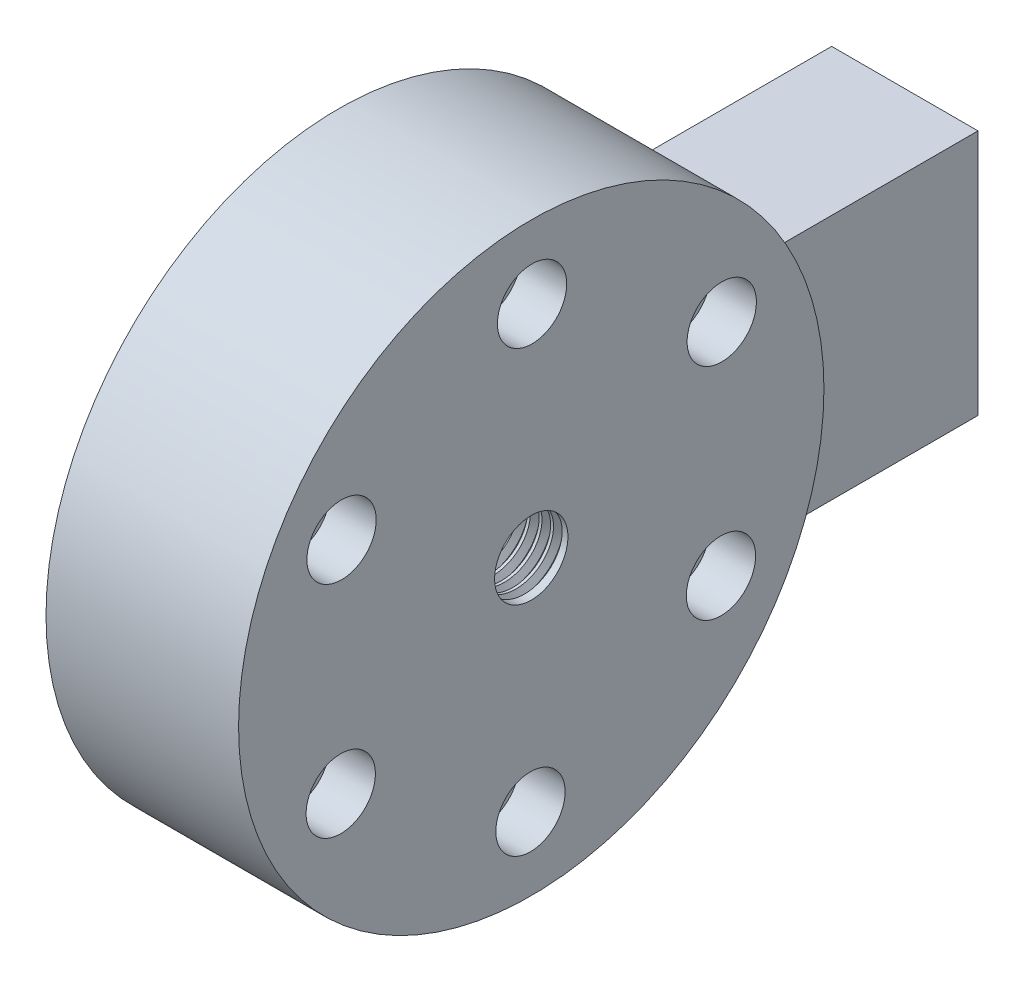
SolidWorks part; units mm, degrees
ref_plane "Front Plane" through (0, 0, 0) normal (0, 0, 1) x (1, 0, 0)
ref_plane "Top Plane" through (0, 0, 0) normal (0, 1, 0) x (1, 0, 0)
ref_plane "Right Plane" through (0, 0, 0) normal (1, 0, 0) x (0, 0, -1)
sketch "Sketch1" plane through (0, 0, 0) normal (1, 0, 0) x (0, 0, -1)
  circle A0 centre (0, 0) radius 38
  dimension "D1" = 76
extrude "Boss-Extrude1" add sketch "Sketch1" along normal blind 25
sketch "Sketch2" plane through (25, 0, 0) normal (1, 0, 0) x (0, 0, -1)
  circle A0 centre (0.1038, 28.4998) radius 3.5
  circle A2 centre (24.7335, 14.16) radius 3.5
  circle A3 centre (24.6297, -14.3398) radius 3.5
  circle A4 centre (-0.1038, -28.4998) radius 3.5
  circle A5 centre (-24.7335, -14.16) radius 3.5
  circle A6 centre (-24.6297, 14.3398) radius 3.5
  circle A9 centre (0, 0) radius 28.5 construction
  dimension "D1" = 7
  dimension "D2" = 57
  dimension "D3" = 6
extrude "Cut-Extrude1" cut sketch "Sketch2" against normal blind 25 contours A0 | A2 | A3 | A4 | A5 | A6
sketch "Sketch3" plane through (25, 0, 0) normal (1, 0, 0) x (0, 0, -1)
  circle A0 centre (0.1038, 28.4998) radius 4.5
  circle A1 centre (0, 0) radius 28.5 construction
  circle A2 centre (0, 0) radius 28.5 construction
  circle A3 centre (24.7335, 14.16) radius 4.5
  circle A4 centre (0, 0) radius 28.5 construction
  circle A5 centre (24.6297, -14.3398) radius 4.5
  circle A6 centre (0, 0) radius 28.5 construction
  circle A7 centre (-0.1038, -28.4998) radius 4.5
  circle A8 centre (0, 0) radius 28.5 construction
  circle A9 centre (-24.7335, -14.16) radius 4.5
  circle A10 centre (0, 0) radius 28.5 construction
  circle A11 centre (-24.6297, 14.3398) radius 4.5
  dimension "D1" = 9
  dimension "D2" = 6
extrude "Cut-Extrude2" cut sketch "Sketch3" against normal blind 6
sketch "Sketch4" plane through (25, 0, 0) normal (1, 0, 0) x (0, 0, -1)
  circle A0 centre (0, 0) radius 4.7625
  dimension "D1" = 9.525
extrude "Cut-Extrude3" cut sketch "Sketch4" against normal through all contours A0
thread "Thread1" pitch 1.5 method cut profile "Thread Profile1" start angle 0, offset 0, length 0, pitch 1.5, diameter 9.525
ref_plane "Plane1" through (25, 0, 4.7625) normal (0, -1, 0) x (0, 0, 1)
sketch "Thread Profile1" plane through (25, 0, 4.7625) normal (0, -1, 0) x (0, 0, 1)
  line L0 (0, 0) -> (0, 1.5) construction
  line L1 (0, 0) -> (0.8119, 0.4687)
  line L2 (0.8119, 0.4687) -> (0.8119, 0.6562)
  line L3 (0.8119, 0.6562) -> (0, 1.125)
  line L4 (0.8119, 0.5625) -> (0, 0.5625) construction
  line L11 (0, 0) -> (0, 1.125)
  point P2 (0, 0)
  dimension "Pitch" = 1.5
  dimension "Profile_Angle" = 60
  dimension "Profile_Land" = 0.1875
  dimension "Profile_Height" = 0.8119
ref_plane "Plane2" through (0, 0, -38) normal (0, 0, 1) x (1, 0, 0)
sketch "Sketch8" plane through (0, 0, -38) normal (0, 0, 1) x (1, 0, 0)
  line L11 (0, 38) -> (0, -38) construction
  line L12 (3, 16) -> (22, 16)
  line L13 (3, 16) -> (3, -16)
  line L14 (3, -16) -> (22, -16)
  line L15 (22, 16) -> (22, -16)
  point P6 (3, 0)
  dimension "D1" = 3
  dimension "D2" = 19
  dimension "D3" = 32
extrude "Boss-Extrude2" add sketch "Sketch8" along normal up to surface and the other way blind 23 up to face at (25, 0, -38)
